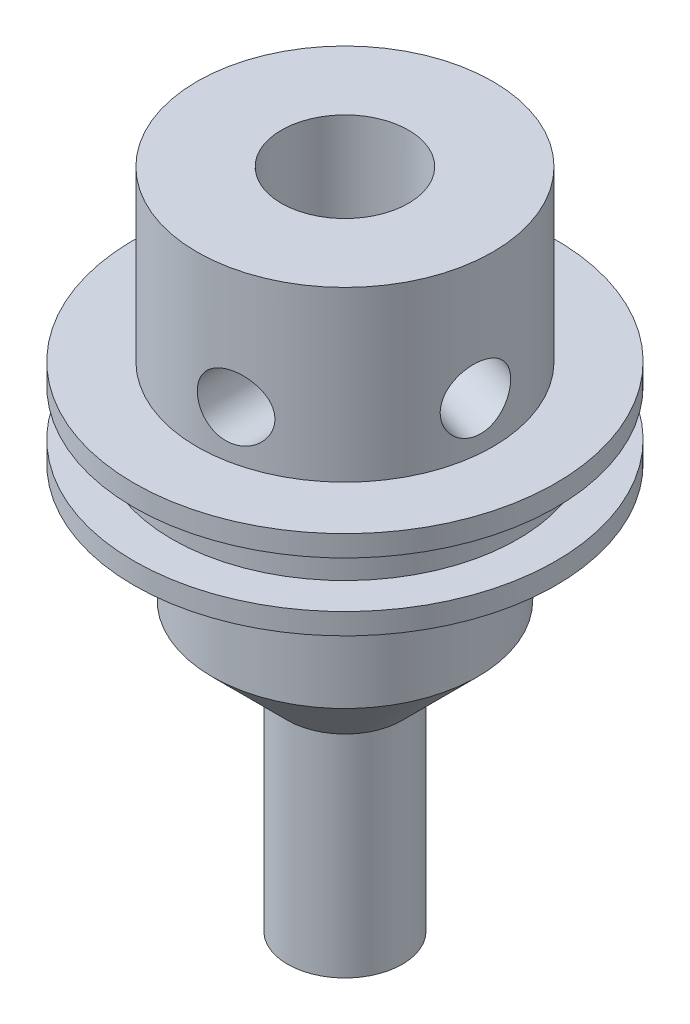
SolidWorks part; units mm, degrees
ref_plane "Front Plane" through (0, 0, 0) normal (0, 0, 1) x (1, 0, 0)
ref_plane "Top Plane" through (0, 0, 0) normal (0, 1, 0) x (1, 0, 0)
ref_plane "Right Plane" through (0, 0, 0) normal (1, 0, 0) x (0, 0, -1)
ref_axis "Centerline" through (0, 55, 0) along (0, -1, 0)
sketch "Sketch2" plane through (0, 0, 0) normal (0, 1, 0) x (1, 0, 0)
  circle A0 centre (0, 0) radius 12.7
  dimension "D1" = 25.4
extrude "Solid Cylinder" add sketch "Sketch2" along normal blind 39.878
sketch "Sketch3" plane through (0, 39.878, 0) normal (0, 1, 0) x (1, 0, 0)
  circle A0 centre (0, 0) radius 2.032
  dimension "D1" = 4.064
extrude "All Through Hole" cut sketch "Sketch3" against normal up to next
sketch "Sketch4" plane through (0, 39.878, 0) normal (0, 1, 0) x (1, 0, 0)
  circle A0 centre (0, 0) radius 3.8252
  dimension "D1" = 7.6505
extrude "Swirl Chamber" cut sketch "Sketch4" against normal blind 19.05
sketch "Sketch5" plane through (0, 39.878, 0) normal (0, 1, 0) x (1, 0, 0)
  circle A0 centre (0, 0) radius 8.9052
  circle A1 centre (0, 0) radius 12.7
  circle A2 centre (0, 0) radius 12.7 construction
  circle A3 centre (0, 0) radius 3.8252 construction
  circle A4 centre (0, 0) radius 3.8252 construction
  dimension "D1" = 5.08
extrude "Top Outer cut" cut sketch "Sketch5" against normal blind 10.16
sketch "Sketch8" plane through (0, 0, 0) normal (0, 0, 1) x (1, 0, 0)
  line L0 (12.7, 0) -> (12.7, 29.718) construction
  line L1 (12.7, 28.448) -> (10.414, 28.448)
  line L2 (12.7, 28.448) -> (12.7, 25.654)
  line L3 (12.7, 25.654) -> (10.414, 25.654)
  line L4 (10.414, 28.448) -> (10.414, 25.654)
  line L5 (12.7, 29.718) -> (-12.7, 29.718) construction
  dimension "D1" = 2.794
  dimension "D2" = 2.286
  dimension "D3" = 1.27
revolve "O Ring Cut" cut sketch "Sketch8" angle 360 about axis through (0, 55, 0) along (0, -1, 0)
sketch "Sketch9" plane through (0, 0, 0) normal (0, 0, 1) x (1, 0, 0)
  line L0 (12.7, 25.654) -> (-12.7, 25.654) construction
  line L1 (12.7, 0) -> (8.001, 0)
  line L2 (12.7, 0) -> (12.7, 24.384)
  line L3 (12.7, 24.384) -> (8.001, 24.384)
  line L4 (8.001, 0) -> (8.001, 24.384)
  dimension "D1" = 4.699
  dimension "D2" = 1.27
revolve "Base Support" cut sketch "Sketch9" angle 360 about axis through (0, 55, 0) along (0, -1, 0)
chamfer "Inner Chamfer" distance 2.54 angle 45 1 edges at (0, 20.828, 2.032)
sketch "Sketch12" plane through (0, 0, 0) normal (0, 0, 1) x (1, 0, 0)
  line L0 (0, 39.878) -> (0, 0) construction
  line L1 (3.8252, 39.878) -> (3.8252, 0) construction
  line L3 (3.8252, 39.878) -> (-3.8252, 39.878) construction
  line L4 (0, 0) -> (3.8252, 0) construction
  line L5 (0, 39.878) -> (3.8252, 39.878) construction
  line L6 (1.9202, 34.544) -> (1.9126, 39.878) construction
  circle A0 centre (1.9202, 32.639) radius 1.905
  dimension "D1" = 3.81
  dimension "D2" = 5.334
extrude "Inlet Hole" cut sketch "Sketch12" along normal up to next
pattern_circular "Inlet Hole Pattern" count 5 over 360 about axis through (0, 55, 0) along (0, -1, 0) of "Inlet Hole"
sketch "Sketch13" plane through (0, 0, 0) normal (0, 0, 1) x (1, 0, 0)
  line L0 (-8.001, 17.272) -> (-3.4544, 12.7254)
  line L1 (-8.001, 24.384) -> (-8.001, 0) construction
  line L2 (-3.4544, 12.7254) -> (-3.4544, 0)
  line L3 (-3.4544, 0) -> (-8.001, 0)
  line L4 (-8.001, 0) -> (-8.001, 17.272)
  line L5 (-8.001, 0) -> (8.001, 0) construction
  line L7 (0, 46.5908) -> (0, -8.5124) construction
  dimension "D1" = 45
  dimension "D2" = 7.112
  dimension "D3" = 3.4544
revolve "Outer Chamfer and Stem" cut sketch "Sketch13" angle 360 about L7
